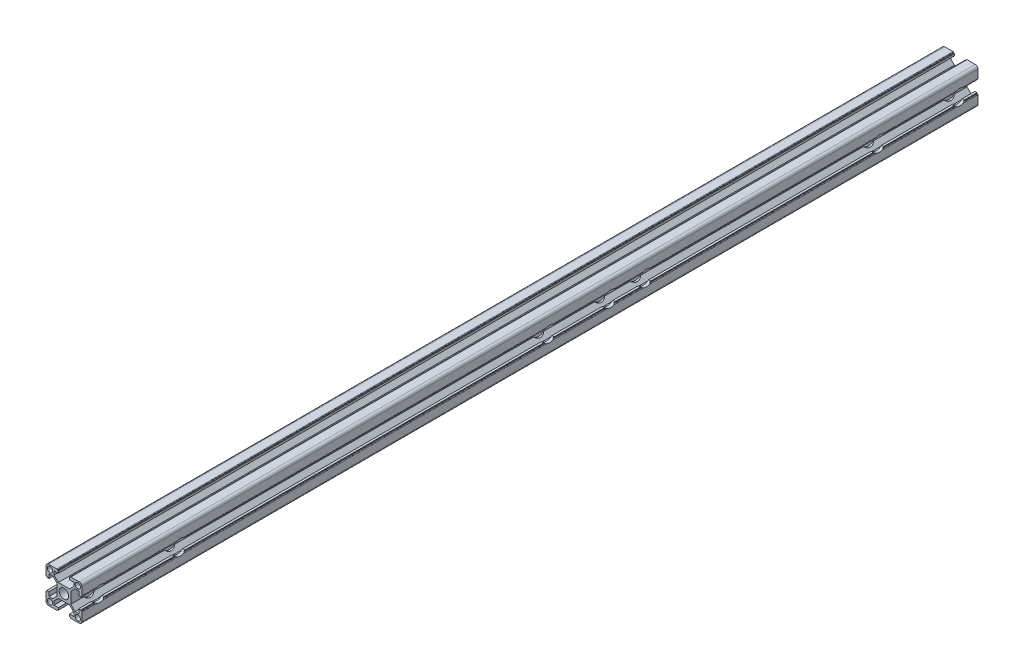
SolidWorks part; units mm, degrees
ref_plane "前视基准面" through (0, 0, 0) normal (0, 0, 1) x (1, 0, 0)
ref_plane "上视基准面" through (0, 0, 0) normal (0, 1, 0) x (1, 0, 0)
ref_plane "右视基准面" through (0, 0, 0) normal (1, 0, 0) x (0, 0, -1)
sketch "草图1" plane through (0, 0, 0) normal (0, 0, 1) x (1, 0, 0)
  line L0 (-7.75, 0) -> (0, 0) construction
  line L1 (7.75, -7.75) -> (-7.75, -7.75) construction
  line L2 (7.75, -7.75) -> (7.75, 7.75) construction
  line L3 (7.75, 7.75) -> (-7.75, 7.75) construction
  line L4 (-7.75, -7.75) -> (-7.75, 7.75) construction
  line L5 (7.75, -7.75) -> (-7.75, 7.75) construction
  line L6 (7.75, 7.75) -> (-7.75, -7.75) construction
  line L7 (0, 0) -> (0, 7.75) construction
  line L8 (3.1429, 3.85) -> (-3.1429, 3.85)
  line L9 (-3.1429, 3.85) -> (-5.5, 6.2071)
  line L10 (-5.5, 6.2071) -> (-5.5, 8.3)
  line L11 (-5.5, 8.3) -> (-3.1, 8.3)
  line L12 (-3.1, 8.3) -> (-3.1, 9.5)
  line L13 (-3.1, 9.5) -> (-3.6, 9.5)
  line L14 (-3.6, 9.5) -> (-3.6, 9.7)
  line L15 (-3.9, 10) -> (-8.5, 10)
  line L16 (-3.85, -3.1429) -> (-3.85, 3.1429)
  line L17 (-3.85, 3.1429) -> (-6.2071, 5.5)
  line L18 (-6.2071, 5.5) -> (-8.3, 5.5)
  line L19 (-8.3, 5.5) -> (-8.3, 3.1)
  line L20 (-9.5, 3.1) -> (-9.5, 3.6)
  line L21 (-8.3, 3.1) -> (-9.5, 3.1)
  line L22 (-9.5, 3.6) -> (-9.7, 3.6)
  line L23 (-10, 3.9) -> (-10, 8.5)
  line L24 (5.5, 8.3) -> (3.1, 8.3)
  line L25 (3.6, 9.5) -> (3.6, 9.7)
  line L26 (3.1, 9.5) -> (3.6, 9.5)
  line L27 (3.1, 8.3) -> (3.1, 9.5)
  line L28 (5.5, 6.2071) -> (5.5, 8.3)
  line L29 (3.1429, 3.85) -> (5.5, 6.2071)
  line L30 (3.85, -3.1429) -> (3.85, 3.1429)
  line L31 (3.85, 3.1429) -> (6.2071, 5.5)
  line L32 (9.5, 3.6) -> (9.7, 3.6)
  line L33 (8.3, 3.1) -> (9.5, 3.1)
  line L34 (9.5, 3.1) -> (9.5, 3.6)
  line L35 (8.3, 5.5) -> (8.3, 3.1)
  line L36 (6.2071, 5.5) -> (8.3, 5.5)
  line L37 (10, 3.9) -> (10, 8.5)
  line L38 (3.9, 10) -> (8.5, 10)
  line L39 (-9.5, -3.6) -> (-9.7, -3.6)
  line L40 (-8.3, -3.1) -> (-9.5, -3.1)
  line L41 (-9.5, -3.1) -> (-9.5, -3.6)
  line L42 (-8.3, -5.5) -> (-8.3, -3.1)
  line L43 (-6.2071, -5.5) -> (-8.3, -5.5)
  line L44 (-3.85, -3.1429) -> (-6.2071, -5.5)
  line L45 (-3.1429, -3.85) -> (-5.5, -6.2071)
  line L46 (-5.5, -6.2071) -> (-5.5, -8.3)
  line L47 (-3.6, -9.5) -> (-3.6, -9.7)
  line L48 (-3.1, -9.5) -> (-3.6, -9.5)
  line L49 (-3.1, -8.3) -> (-3.1, -9.5)
  line L50 (-5.5, -8.3) -> (-3.1, -8.3)
  line L51 (5.5, -6.2071) -> (5.5, -8.3)
  line L52 (3.1, -8.3) -> (3.1, -9.5)
  line L53 (3.1, -9.5) -> (3.6, -9.5)
  line L54 (3.6, -9.5) -> (3.6, -9.7)
  line L55 (5.5, -8.3) -> (3.1, -8.3)
  line L56 (3.1429, -3.85) -> (5.5, -6.2071)
  line L57 (3.1429, -3.85) -> (-3.1429, -3.85)
  line L58 (3.85, -3.1429) -> (6.2071, -5.5)
  line L59 (6.2071, -5.5) -> (8.3, -5.5)
  line L60 (8.3, -5.5) -> (8.3, -3.1)
  line L61 (9.5, -3.1) -> (9.5, -3.6)
  line L62 (8.3, -3.1) -> (9.5, -3.1)
  line L63 (9.5, -3.6) -> (9.7, -3.6)
  line L64 (3.9, -10) -> (8.5, -10)
  line L65 (10, -3.9) -> (10, -8.5)
  line L66 (-10, -3.9) -> (-10, -8.5)
  line L67 (-3.9, -10) -> (-8.5, -10)
  circle A0 centre (0, 0) radius 2.65
  circle A1 centre (-7.75, 7.75) radius 1.5
  circle A2 centre (7.75, 7.75) radius 1.5
  circle A3 centre (7.75, -7.75) radius 1.5
  circle A4 centre (-7.75, -7.75) radius 1.5
  arc A5 (-10, -8.5) -> (-8.5, -10) centre (-8.5, -8.5) ccw
  arc A6 (8.5, -10) -> (10, -8.5) centre (8.5, -8.5) ccw
  arc A7 (10, 8.5) -> (8.5, 10) centre (8.5, 8.5) ccw
  arc A8 (-8.5, 10) -> (-10, 8.5) centre (-8.5, 8.5) ccw
  arc A9 (3.6, -9.7) -> (3.9, -10) centre (3.9, -9.7) ccw
  arc A10 (-3.6, -9.7) -> (-3.9, -10) centre (-3.9, -9.7) cw
  arc A11 (-9.7, -3.6) -> (-10, -3.9) centre (-9.7, -3.9) ccw
  arc A12 (9.7, -3.6) -> (10, -3.9) centre (9.7, -3.9) cw
  arc A13 (9.7, 3.6) -> (10, 3.9) centre (9.7, 3.9) ccw
  arc A14 (-9.7, 3.6) -> (-10, 3.9) centre (-9.7, 3.9) cw
  arc A15 (3.6, 9.7) -> (3.9, 10) centre (3.9, 9.7) cw
  arc A16 (-3.6, 9.7) -> (-3.9, 10) centre (-3.9, 9.7) ccw
  point P46 (0, 3.85)
  point P56 (-3.85, 0)
  point P78 (3.85, 0)
  point P87 (-10, -10)
  point P90 (10, -10)
  point P93 (10, 10)
  point P96 (-10, 10)
  point P99 (3.6, -10)
  point P102 (-3.6, -10)
  point P105 (-10, -3.6)
  point P108 (10, -3.6)
  point P111 (10, 3.6)
  point P114 (-10, 3.6)
  point P117 (3.6, 10)
  point P120 (-3.6, 10)
  dimension "D1" = 5.3
  dimension "D2" = 3
  dimension "D11" = 1.5
  dimension "D12" = 2.25
  dimension "D13" = 0.3
  dimension "D3" = 7.7
  dimension "D4" = 6.2
  dimension "D5" = 1.7
  dimension "D6" = 1.2
  dimension "D7" = 20
  dimension "D8" = 7.2
  dimension "D9" = 11
  dimension "D10" = 1
extrude "凸台-拉伸1" add sketch "草图1" along normal mid plane 500
sketch "草图4" plane through (3.85, 0, 0) normal (1, 0, 0) x (0, 0, -1)
  line L0 (240, 0) -> (-240, 0) construction
  line L1 (-250, -3.1429) -> (-250, 3.1429) construction
  circle A0 centre (-240, 0) radius 2
  circle A1 centre (240, 0) radius 2
  circle A6 centre (-195, 0) radius 2
  circle A7 centre (195, 0) radius 2
  circle A8 centre (65, 0) radius 2
  point P4 (0, 0)
  dimension "D1" = 4
  dimension "D2" = 10
  dimension "D3" = 45
  dimension "D4" = 45
  dimension "D5" = 130
extrude "切除-拉伸3" cut sketch "草图4" against normal through all
sketch "草图5" plane through (3.85, 0, 0) normal (1, 0, 0) x (0, 0, -1)
  circle A0 centre (195, 0) radius 4.25
  circle A1 centre (240, 0) radius 4.25
  circle A2 centre (65, 0) radius 4.25
  circle A3 centre (-240, 0) radius 4.25
  circle A4 centre (-195, 0) radius 4.25
  dimension "D1" = 8.5
extrude "切除-拉伸4" cut sketch "草图5" along normal through all
sketch "草图6" plane through (3.85, 0, 0) normal (1, 0, 0) x (0, 0, -1)
  circle A0 centre (45, 0) radius 2
  circle A1 centre (65, 0) radius 2 construction
  circle A2 centre (11, 0) radius 2
  dimension "D1" = 20
  dimension "D2" = 34
extrude "切除-拉伸5" cut sketch "草图6" against normal through all
sketch "草图7" plane through (3.85, 0, 0) normal (1, 0, 0) x (0, 0, -1)
  circle A0 centre (45, 0) radius 4.25
  circle A2 centre (11, 0) radius 4.25
  arc A3 (66.6889, 3.9) -> (63.3111, 3.9) centre (65, 0) ccw construction
extrude "切除-拉伸6" cut sketch "草图7" along normal through all
sketch "草图8" plane through (3.85, 0, 0) normal (1, 0, 0) x (0, 0, -1)
  circle A0 centre (-43, 0) radius 2.1
  circle A1 centre (-9, 0) radius 2.1
  circle A2 centre (11, 0) radius 2 construction
  dimension "D1" = 34
  dimension "D2" = 4.2
  dimension "D3" = 20
extrude "切除-拉伸7" cut sketch "草图8" against normal through all
sketch "草图9" plane through (-3.85, 0, 0) normal (-1, 0, 0) x (0, 0, 1)
  circle A0 centre (9, 0) radius 4.25
  circle A1 centre (43, 0) radius 4.25
  dimension "D1" = 8.5
extrude "切除-拉伸8" cut sketch "草图9" along normal through all
equation "\"D4@草图4\"=\"D3@草图4\""
